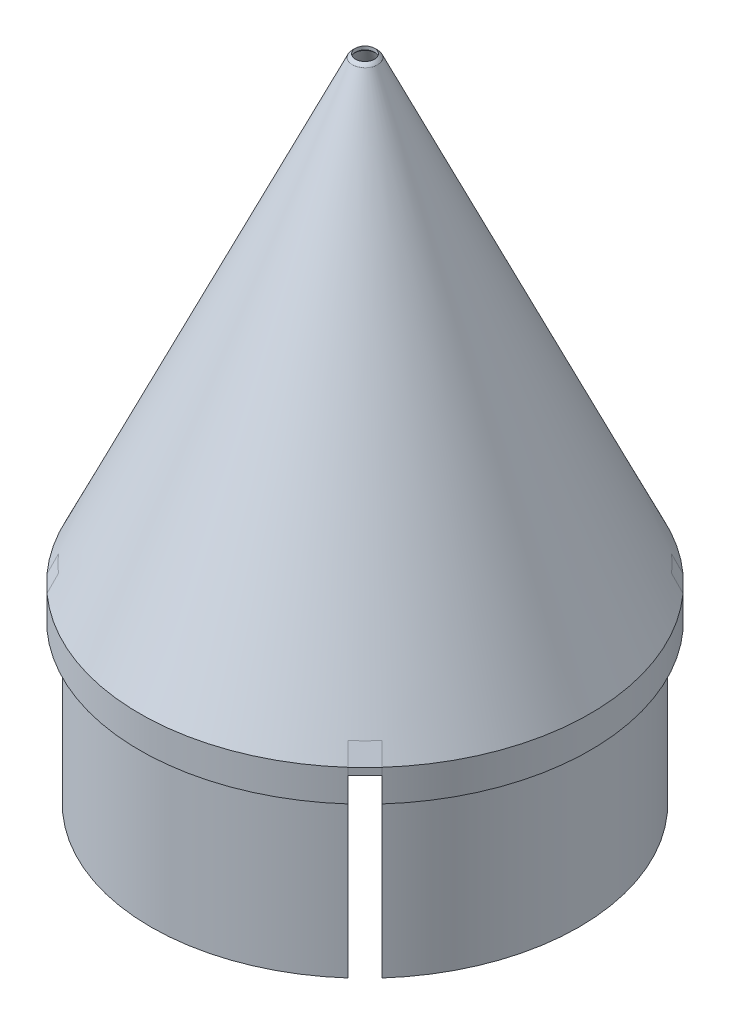
SolidWorks part; units mm, degrees
ref_plane "Front Plane" through (0, 0, 0) normal (0, 0, 1) x (1, 0, 0)
ref_plane "Top Plane" through (0, 0, 0) normal (0, 1, 0) x (1, 0, 0)
ref_plane "Right Plane" through (0, 0, 0) normal (1, 0, 0) x (0, 0, -1)
sketch "Sketch3" plane through (0, 0, 0) normal (0, 0, 1) x (1, 0, 0)
  line L1 (0, 0) -> (0, 155.682)
  line L4 (0, 0) -> (0, -50)
  line L5 (0, -50) -> (67.5, -50)
  line L6 (67.5, -50) -> (67.5, 0)
  line L9 (71, 0) -> (71, 10)
  line L11 (67.5, 0) -> (71, 0)
  line L12 (4, 153.682) -> (71, 10)
  line L13 (0, 229.1763) -> (0, 65.794) construction
  arc A0 (0, 155.682) -> (4, 153.682) centre (0, 150.682) cw
  point P11 (67.5, -50)
  point P14 (71, 10)
  dimension "Round yDim" = 2
  dimension "Lip Height" = 10
  dimension "Shoulder Height" = 50
  dimension "Half Angle" = 25
  dimension "Shoulder Diam" = 135
  dimension "Outer Diam" = 142
  dimension "Round xDim" = 8
revolve "Revolve1" add sketch "Sketch3" angle 360 about L1
shell "Shell1" thickness 0.8 removed face at (0, -50, -67.5)
sketch "Sketch7" plane through (0, 0, 0) normal (0, 1, 0) x (1, 0, 0)
  circle A0 centre (0, 0) radius 3
  dimension "PitotHoleDiam" = 6
extrude "Cut-Extrude3" cut sketch "Sketch7" along normal through all
ref_plane "Plane1" through (0, 0, 0) normal (1, 0, 0) x (0, 0, -1)
sketch "Sketch8" plane through (0, 0, 0) normal (1, 0, 0) x (0, 0, -1)
  line L0 (-39.807, 40.9099) -> (-39.807, 20) construction
  line L1 (-44.807, 44.0901) -> (-44.807, 39.0901) construction
  line L2 (-44.807, 39.0901) -> (-39.807, 40.9099) construction
  line L3 (-39.807, 40.9099) -> (-39.807, 35.9099)
  line L4 (-44.807, 44.0901) -> (-44.807, 39.0901)
  line L5 (-44.807, 39.0901) -> (-39.807, 40.9099)
  line L6 (-39.807, 35.9099) -> (-44.807, 34.0901)
  line L7 (-44.807, 34.0901) -> (-58.8839, 34.0901)
  line L8 (-3.3116, 153.2652) -> (-70.2, 9.8226) construction
  line L9 (-58.8839, 34.0901) -> (-44.807, 64.2781)
  line L10 (-44.807, 64.2781) -> (-44.807, 44.0901)
  dimension "D1" = 5
extrude "Boss-Extrude1" add sketch "Sketch8" along normal mid plane 15
sketch "Sketch9" plane through (0, 0, 0) normal (1, 0, 0) x (0, 0, -1)
  line L0 (-44.807, 39.0901) -> (-44.807, 62.9414) construction
  line L1 (-39.807, 40.9099) -> (-44.807, 39.0901) construction
  line L2 (-39.807, 35.9099) -> (-39.807, 40.9099) construction
  line L3 (-44.807, 34.0901) -> (-39.807, 35.9099) construction
  line L5 (-44.807, 39.0901) -> (-44.807, 62.9414)
  line L6 (-39.807, 40.9099) -> (-44.807, 39.0901)
  line L7 (-39.807, 35.9099) -> (-39.807, 40.9099)
  line L8 (-44.807, 34.0901) -> (-39.807, 35.9099)
  line L9 (-58.8839, 34.0901) -> (-44.807, 34.0901)
  line L10 (-44.807, 34.0901) -> (-44.807, 39.0901) construction
  line L11 (-44.807, 62.9414) -> (-58.8839, 34.0901)
extrude "Cut-Extrude4" cut sketch "Sketch9" against normal mid plane 3.5
pattern_circular "CirPattern1" count 2 over 360 about axis through (0, 0, 0) along (0, -1, 0) of "Boss-Extrude1", "Cut-Extrude4"
ref_axis "Axis1" through (0, 0, 0) along (0, -1, 0)
ref_plane "Plane2" through (0, 0, 0) normal (0.7071, 0, 0.7071) x (0, -1, 0)
sketch "Sketch11" plane through (0, 0, 0) normal (0.7071, 0, 0.7071) x (0, -1, 0)
  line L0 (-12.58, 59.0623) -> (-16.4367, 63.6586) construction
  line L1 (-16.4367, 63.6586) -> (-1.1158, 76.5143) construction
  line L2 (-1.1158, 76.5143) -> (2.7409, 71.9181) construction
  line L3 (2.7409, 71.9181) -> (-12.58, 59.0623) construction
  line L4 (-14.5083, 61.3604) -> (0.8126, 74.2162) construction
  line L5 (-8.0805, 66.7) -> (-0.8, 66.7) construction
  line L6 (-15.3609, 53.7) -> (-15.3609, 67.3869)
  line L7 (-15.3609, 67.3869) -> (-9.8226, 70.2)
  line L8 (-8.0805, 53.7) -> (-13.9678, 65.2905) construction
  line L9 (-13.9678, 65.2905) -> (-15.0999, 67.5194) construction
  line L10 (-9.8226, 70.2) -> (-153.9335, -3) construction
  line L11 (-9.8226, 70.2) -> (-0.8, 70.2)
  line L15 (0, 0) -> (50, 0) construction
  line L16 (-0.8, 53.7) -> (-0.8, 66.7)
  line L17 (-0.8, 66.7) -> (-0.8, 70.2)
  circle A2 centre (-8.0805, 53.7) radius 13 construction
  circle A3 centre (-8.0805, 53.7) radius 10 construction
  arc A4 (-15.3609, 53.7) -> (-0.8, 53.7) centre (-8.0805, 53.7) ccw
  point P6 (-14.5083, 61.3604)
  dimension "Arm Wheel Diam Mock" = 20
  dimension "D4" = 2.5
  dimension "Arm Wheel Arm Width Mock" = 6
  dimension "Arm Wheel Arm Length Mock" = 20
  dimension "ArmAngle" = 40
extrude "Boss-Extrude3" add sketch "Sketch11" along normal mid plane 20
sketch "Sketch13" plane through (0, -50, 0) normal (0, -1, 0) x (1, 0, 0)
  line L0 (39.8946, -25.7525) -> (25.7525, -39.8946) construction
  line L1 (30.1719, -35.4752) -> (35.4752, -30.1719)
  line L2 (30.1719, -35.4752) -> (47.4829, -52.7862)
  line L3 (35.4752, -30.1719) -> (52.7862, -47.4829)
  arc A0 (47.4829, -52.7862) -> (52.7862, -47.4829) centre (0, 0) ccw
  circle A1 centre (0, 0) radius 71 construction
  point P11 (32.8236, -32.8236)
  point P12 (32.8236, -32.8236)
  dimension "ArmCutoutWidth" = 7.5
extrude "Cut-Extrude8" cut sketch "Sketch13" against normal blind 65.5
hole_wizard "M4 Clearance Hole1" positions "Sketch14" profile "Sketch15" hole size "M4" standard "ANSI Metric"
sketch "Sketch14" plane through (7.0711, 0, 7.0711) normal (0.7071, 0, 0.7071) x (0.7071, 0, -0.7071)
  arc A0 (53.7, 15.3609) -> (53.7, 0.8) centre (53.7, 8.0805) ccw construction
  point P0 (53.7, 8.0805)
sketch "Sketch15" plane through (45.0427, 8.0805, -30.9006) normal (0, 1, 0) x (0.7071, 0, -0.7071)
  line L0 (0, 0) -> (0, 21.4421)
  line L1 (0, 21.4421) -> (2.4, 20)
  line L2 (2.4, 20) -> (2.4, 0)
  line L5 (2.4, 0) -> (0, 0)
  line L10 (0, 21.4421) -> (-2.4, 20) construction
  line L11 (0, -6.35) -> (0, 107.95) construction
  dimension "Hole Dia." = 4.8
  dimension "Hole Depth" = 20
  dimension "Drill Angle" = 118
sketch "Sketch17" plane through (0, 0, 0) normal (0.7071, 0, 0.7071) x (0, -1, 0)
  line L0 (-15.5, 67.5526) -> (-153.2652, 3.3116) construction
  line L1 (-64.9908, 44.4747) -> (-52.1813, 50.4478)
  line L4 (-52.1413, 45.5988) -> (-64.9908, 44.4747)
  line L5 (-52.1813, 50.4478) -> (-50.9126, 47.7271)
  arc A0 (-52.1413, 45.5988) -> (-50.9126, 47.7271) centre (-52.272, 47.0931) ccw
  circle A1 centre (-52.272, 47.0931) radius 0.75
  point P11 (0, 0)
  dimension "D1" = 1.5
  dimension "D2" = 1.5
  dimension "D4" = 20
  dimension "D5" = 3.002
  dimension "D6" = 40.4733
extrude "Boss-Extrude4" add sketch "Sketch17" along normal mid plane 2.5
sketch "Sketch19" plane through (-7.0711, 0, -7.0711) normal (-0.7071, 0, -0.7071) x (-0.7071, 0, 0.7071)
  line L0 (-53.7, 8.0805) -> (-44.7, 8.0805) construction
  line L1 (-44.7, 12.8305) -> (-48.1825, 12.8305)
  line L2 (-44.7, 3.3305) -> (-48.1825, 3.3305)
  arc A0 (-53.7, 0.8) -> (-53.7, 15.3609) centre (-53.7, 8.0805) ccw construction
  arc A1 (-48.1825, 3.3305) -> (-48.1825, 12.8305) centre (-53.7, 8.0805) ccw
  circle A2 centre (-44.7, 8.0805) radius 2.75 construction
  arc A3 (-44.7, 3.3305) -> (-44.7, 12.8305) centre (-44.7, 8.0805) ccw
  dimension "D1" = 5.5
  dimension "D2" = 2
  dimension "D3" = 9
extrude "Boss-Extrude7" add sketch "Sketch19" against normal blind 6.25
sketch "Sketch21" plane through (-7.0711, 0, -7.0711) normal (-0.7071, 0, -0.7071) x (-0.7071, 0, 0.7071)
  circle A0 centre (-44.7, 8.0805) radius 2.8
  arc A1 (-44.7, 3.3305) -> (-44.7, 12.8305) centre (-44.7, 8.0805) ccw construction
  dimension "D1" = 5.6
extrude "Cut-Extrude9" cut sketch "Sketch21" against normal up to next
sketch "Sketch22" plane through (-7.0711, 0, -7.0711) normal (-0.7071, 0, -0.7071) x (-0.7071, 0, 0.7071)
  circle A0 centre (-44.7, 8.0805) radius 4.75
  arc A1 (-44.7, 3.3305) -> (-44.7, 12.8305) centre (-44.7, 8.0805) ccw construction
  circle A2 centre (-44.7, 8.0805) radius 2.8 construction
  circle A3 centre (-44.7, 8.0805) radius 2.8
extrude "Boss-Extrude8" add sketch "Sketch22" along normal blind 4
sketch "Sketch23" plane through (-9.8995, 0, -9.8995) normal (-0.7071, 0, -0.7071) x (-0.7071, 0, 0.7071)
  circle A0 centre (-44.7, 8.0805) radius 4.75 construction
  circle A1 centre (-44.7, 8.0805) radius 4.75
  circle A2 centre (-44.7, 8.0805) radius 2.3
  dimension "D1" = 4.6
extrude "Boss-Extrude9" add sketch "Sketch23" along normal blind 2
pattern_circular "CirPattern4" count 4 over 360 about axis through (0, 0, 0) along (0, -1, 0) of "M4 Clearance Hole1", "Boss-Extrude3", "Boss-Extrude4", "Cut-Extrude8", "Boss-Extrude7", "Cut-Extrude9", "Boss-Extrude8", "Boss-Extrude9"
sketch "Sketch18" plane through (1.9445, 0, -7.2478) normal (0.7071, 0, 0.7071) x (0.7071, 0, -0.7071)
  line L0 (61.8325, 15.5) -> (64.4009, 10)
  line L1 (64.4009, 10) -> (64.4009, 7.8056)
  line L2 (64.4009, 10) -> (64.4009, 0) construction
  line L3 (64.4009, 7.8056) -> (62.5843, 9.9705)
  line L6 (60.9484, 15.5) -> (61.8325, 15.5)
  line L7 (62.5843, 9.9705) -> (62.5843, 5.3699) construction
  circle A1 centre (47.2, 8.0805) radius 13.0974 construction
  circle A3 centre (47.2, 8.0805) radius 2.4 construction
  arc A4 (60.2, 9.5805) -> (58.7, 11.0805) centre (58.7, 9.5805) ccw construction
  arc A6 (62.5843, 9.9705) -> (60.9484, 15.5) centre (52.4213, 9.9705) ccw
  dimension "D1" = 13.0974
  dimension "D2" = 13
  dimension "ArmStopperAngle" = 40
  dimension "D4" = 15.5
extrude "Boss-Extrude6" add sketch "Sketch18" along normal up to next
pattern_circular "CirPattern8" count 4 over 360 about axis through (0, 0, 0) along (0, -1, 0) of "Boss-Extrude6"
equation "\"LegAngle\"=30"
